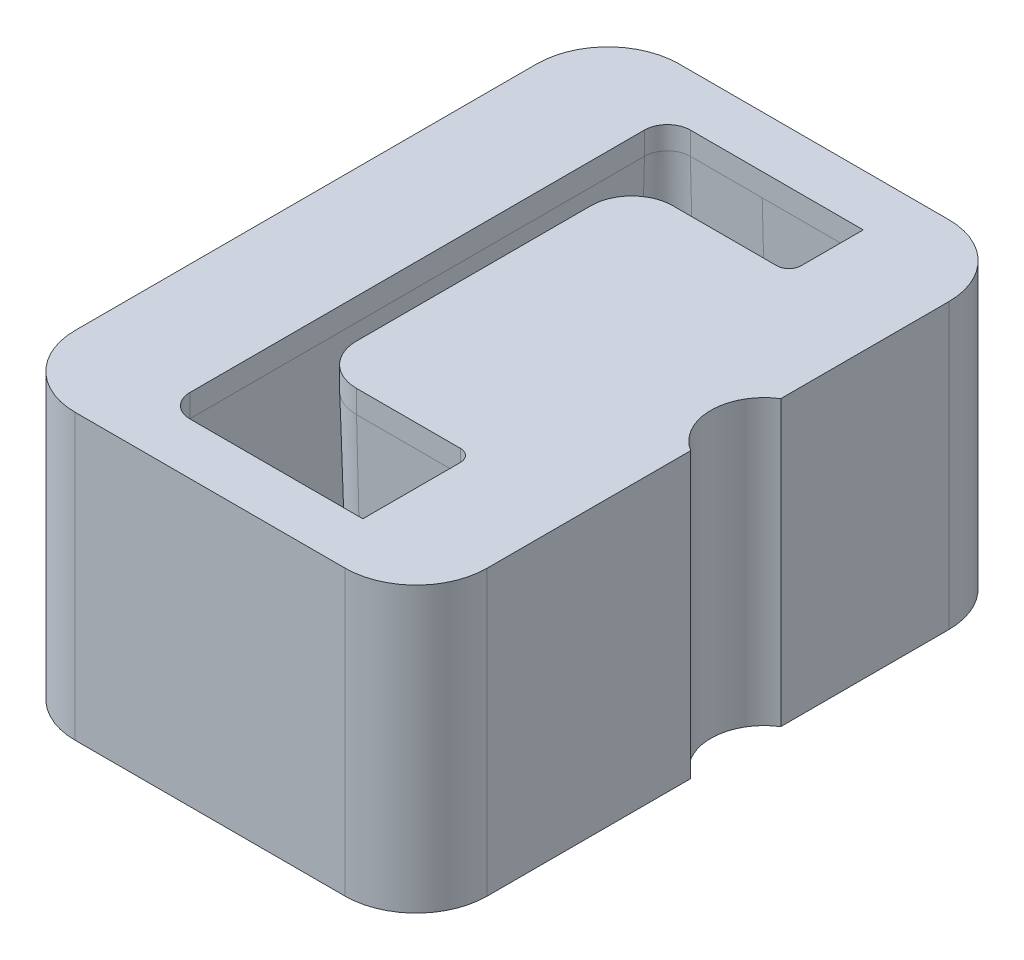
SolidWorks part; units mm, degrees
material "K110"
ref_plane "Front Plane" through (0, 0, 0) normal (0, 0, 1) x (1, 0, 0)
ref_plane "Top Plane" through (0, 0, 0) normal (0, 1, 0) x (1, 0, 0)
ref_plane "Right Plane" through (0, 0, 0) normal (1, 0, 0) x (0, 0, -1)
sketch "Sketch1" plane through (0, 0, 0) normal (0, 1, 0) x (1, 0, 0)
  line L1 (-29, -42.5) -> (29, -42.5)
  line L2 (-29, -42.5) -> (-29, 42.5)
  line L3 (-29, 42.5) -> (29, 42.5)
  line L4 (29, -42.5) -> (29, 42.5)
  line L5 (-29, -42.5) -> (29, 42.5) construction
  line L6 (-29, 42.5) -> (29, -42.5) construction
  point P0 (0, 0)
  dimension "D1" = 85
  dimension "D2" = 58
extrude "Boss-Extrude1" add sketch "Sketch1" against normal blind 40
fillet "Fillet1" radius 10 4 edges at (-29, -20, -42.5) (29, -20, -42.5) (29, -20, 42.5) (-29, -20, 42.5)
sketch "Sketch2" plane through (0, 0, 0) normal (0, 1, 0) x (1, 0, 0)
  line L16 (14.23, 35.23) -> (-10.12, 35.23)
  line L17 (-13.35, 32) -> (-13.35, -32)
  line L18 (-10.12, -35.23) -> (14.23, -35.23)
  line L19 (14.23, -35.23) -> (14.23, -21.5)
  line L20 (12.5, -19.77) -> (-2.12, -19.77)
  line L21 (-7.89, -14) -> (-7.89, 19)
  line L22 (-2.12, 24.77) -> (12.5, 24.77)
  line L23 (14.23, 26.5) -> (14.23, 35.23)
  line L24 (14.23, 35.23) -> (-10.12, 35.23)
  line L25 (-13.35, 32) -> (-13.35, -32)
  line L26 (-10.12, -35.23) -> (14.23, -35.23)
  line L27 (14.23, -35.23) -> (14.23, -21.5)
  line L28 (12.5, -19.77) -> (-2.12, -19.77)
  line L29 (-7.89, -14) -> (-7.89, 19)
  line L30 (-2.12, 24.77) -> (12.5, 24.77)
  line L31 (14.23, 26.5) -> (14.23, 35.23)
  arc A12 (-10.12, 35.23) -> (-13.35, 32) centre (-10.12, 32) ccw
  arc A13 (-13.35, -32) -> (-10.12, -35.23) centre (-10.12, -32) ccw
  arc A14 (14.23, -21.5) -> (12.5, -19.77) centre (12.5, -21.5) ccw
  arc A15 (-7.89, -14) -> (-2.12, -19.77) centre (-2.12, -14) ccw
  arc A16 (-2.12, 24.77) -> (-7.89, 19) centre (-2.12, 19) ccw
  arc A17 (12.5, 24.77) -> (14.23, 26.5) centre (12.5, 26.5) ccw
  arc A18 (-10.12, 35.23) -> (-13.35, 32) centre (-10.12, 32) ccw
  arc A19 (-13.35, -32) -> (-10.12, -35.23) centre (-10.12, -32) ccw
  arc A20 (14.23, -21.5) -> (12.5, -19.77) centre (12.5, -21.5) ccw
  arc A21 (-7.89, -14) -> (-2.12, -19.77) centre (-2.12, -14) ccw
  arc A22 (-2.12, 24.77) -> (-7.89, 19) centre (-2.12, 19) ccw
  arc A23 (12.5, 24.77) -> (14.23, 26.5) centre (12.5, 26.5) ccw
  dimension "D1" = 0.23
extrude "Cut-Extrude1" cut sketch "Sketch2" against normal up to next
sketch "Sketch3" plane through (0, 0, 0) normal (1, 0, 0) x (0, 0, -1)
  line L0 (35.23, -3.2) -> (36.1936, -40)
  line L1 (35.23, -40) -> (35.23, 0) construction
  line L2 (32.5, -40) -> (42.5, -40) construction
  line L3 (36.1936, -40) -> (35.23, -40)
  line L4 (35.23, -40) -> (35.23, -3.2)
  line L5 (31.9, 0) -> (-31.9, 0) construction
  dimension "D1" = 3.2
  dimension "D2" = 1.5
sketch "Sketch5" plane through (0, 0, 0) normal (0, 1, 0) x (1, 0, 0)
  line L0 (12.5, -19.77) -> (-2.12, -19.77) construction
  line L1 (14.23, -35.23) -> (14.23, -21.5) construction
  line L2 (-10.12, -35.23) -> (14.23, -35.23) construction
  line L3 (-7.89, -14) -> (-7.89, 19) construction
  line L4 (-2.12, 24.77) -> (12.5, 24.77) construction
  line L5 (-13.35, 32) -> (-13.35, -32) construction
  line L6 (14.23, 35.23) -> (-10.12, 35.23) construction
  line L7 (14.23, 26.5) -> (14.23, 35.23) construction
  line L8 (12.5, -19.77) -> (-2.12, -19.77)
  line L9 (14.23, -35.23) -> (14.23, -21.5)
  line L10 (-10.12, -35.23) -> (14.23, -35.23)
  line L11 (-7.89, -14) -> (-7.89, 19)
  line L12 (-2.12, 24.77) -> (12.5, 24.77)
  line L13 (-13.35, 32) -> (-13.35, -32)
  line L14 (14.23, 35.23) -> (-10.12, 35.23)
  line L15 (14.23, 26.5) -> (14.23, 35.23)
  arc A0 (-7.89, -14) -> (-2.12, -19.77) centre (-2.12, -14) ccw construction
  arc A1 (14.23, -21.5) -> (12.5, -19.77) centre (12.5, -21.5) ccw construction
  arc A2 (-13.35, -32) -> (-10.12, -35.23) centre (-10.12, -32) ccw construction
  arc A3 (-2.12, 24.77) -> (-7.89, 19) centre (-2.12, 19) ccw construction
  arc A4 (-10.12, 35.23) -> (-13.35, 32) centre (-10.12, 32) ccw construction
  arc A5 (12.5, 24.77) -> (14.23, 26.5) centre (12.5, 26.5) ccw construction
  arc A6 (-7.89, -14) -> (-2.12, -19.77) centre (-2.12, -14) ccw
  arc A7 (14.23, -21.5) -> (12.5, -19.77) centre (12.5, -21.5) ccw
  arc A8 (-13.35, -32) -> (-10.12, -35.23) centre (-10.12, -32) ccw
  arc A9 (-2.12, 24.77) -> (-7.89, 19) centre (-2.12, 19) ccw
  arc A10 (-10.12, 35.23) -> (-13.35, 32) centre (-10.12, 32) ccw
  arc A11 (12.5, 24.77) -> (14.23, 26.5) centre (12.5, 26.5) ccw
sweep "Cut-Sweep1" cut profiles "Sketch3" path "Sketch5"
hole_wizard "M6 Tapped Hole1" positions "Sketch8" profile "Sketch7" tap size "M6" standard "ISO"
sketch "Sketch8" plane through (0, -40, 0) normal (0, -1, 0) x (-1, 0, 0)
  line L0 (-19, 42.5) -> (19, 42.5) construction
  line L1 (-29, -32.5) -> (-29, 32.5) construction
  line L2 (29, 32.5) -> (29, -32.5) construction
  line L3 (19, -42.5) -> (-19, -42.5) construction
  point P0 (-22, 35.5)
  point P2 (22, 35.5)
  point P4 (22, -35.5)
  point P6 (-22, -35.5)
  dimension "D1" = 7
  dimension "D2" = 7
  dimension "D3" = 7
  dimension "D4" = 7
sketch "Sketch7" plane through (22, -40, -35.5) normal (1, 0, 0) x (0, 0, -1)
  line L0 (0, 0) -> (0, 18.5022)
  line L1 (0, 18.5022) -> (2.5, 17)
  line L2 (2.5, 17) -> (2.5, 0.525)
  line L3 (2.5, 0.525) -> (3.025, 0)
  line L5 (3.025, 0) -> (0, 0)
  line L6 (-2.5, 0.525) -> (-3.025, 0) construction
  line L10 (0, 18.5022) -> (-2.5, 17) construction
  line L11 (0, -6.35) -> (0, 107.95) construction
  dimension "Tap Drill Dia." = 5
  dimension "Tap Drill Depth" = 17
  dimension "Near C'Sink Dia." = 6.05
  dimension "Near C'Sink Angle" = 90
  dimension "Drill Angle" = 118
cosmetic thread "Hole Thread1" parameters "D1"=12, "D2"=6
cosmetic thread "Hole Thread2" parameters "D1"=12, "D2"=6
cosmetic thread "Hole Thread3" parameters "D1"=12, "D2"=6
cosmetic thread "Hole Thread4" parameters "D1"=12, "D2"=6
extrude "Cut-Extrude2" cut sketch "Sketch9" against normal through all
sketch "Sketch9" plane through (296.88, 0, 7.73) normal (0, 1, 0) x (1, 0, 0)
  circle A0 centre (-263.88, 10.23) radius 7.5
